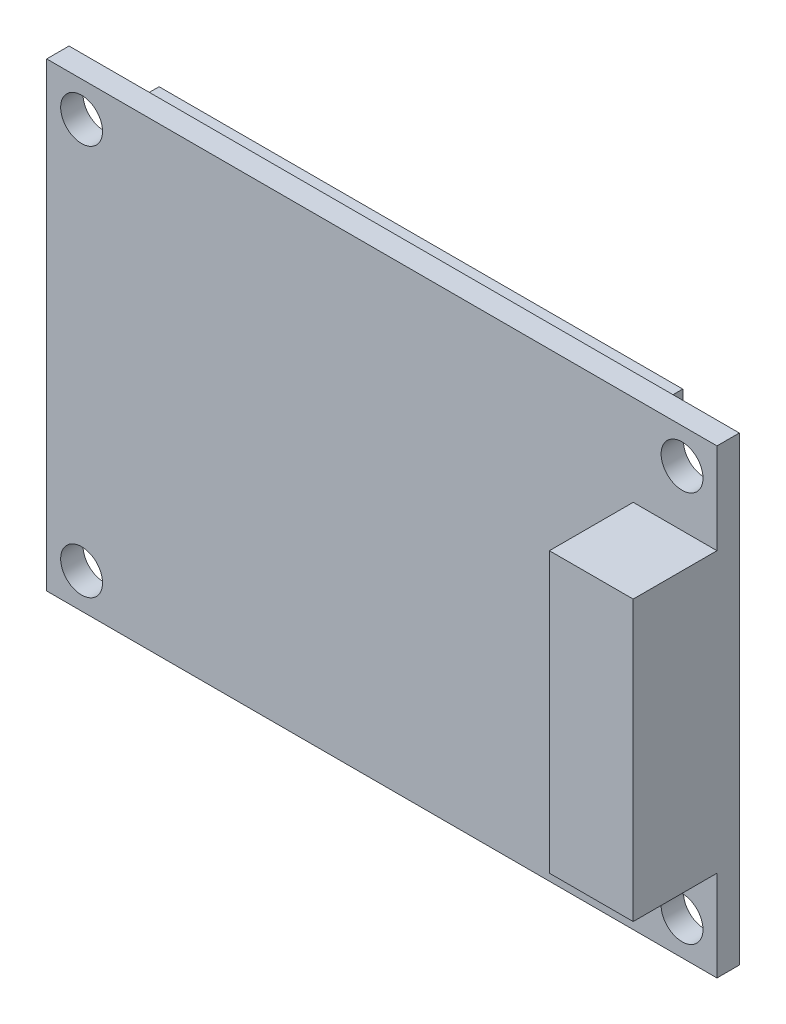
SolidWorks part; units mm, degrees
ref_plane "Plan de face" through (0, 0, 0) normal (0, 0, 1) x (1, 0, 0)
ref_plane "Plan de dessus" through (0, 0, 0) normal (0, 1, 0) x (1, 0, 0)
ref_plane "Plan de droite" through (0, 0, 0) normal (1, 0, 0) x (0, 0, -1)
sketch "BASE PCB" plane through (0, 0, 0) normal (0, 0, 1) x (1, 0, 0)
  line L0 (0, -18.15) -> (0, 18.15) construction
  line L1 (24, 16.5) -> (-24, 16.5)
  line L2 (24, 16.5) -> (24, -16.5)
  line L3 (24, -16.5) -> (-24, -16.5)
  line L4 (-24, 16.5) -> (-24, -16.5)
  line L5 (24, 16.5) -> (-24, -16.5) construction
  line L6 (24, -16.5) -> (-24, 16.5) construction
  line L8 (24, 10) -> (18, 10) construction
  line L9 (24, 10) -> (24, -10) construction
  line L10 (24, -10) -> (18, -10) construction
  line L11 (18, 10) -> (18, -10) construction
  circle A0 centre (-21.5, 14) radius 1.5
  circle A1 centre (-21.5, -14) radius 1.5
  circle A2 centre (21.5, -14) radius 1.5
  circle A3 centre (21.5, 14) radius 1.5
  point P0 (0, 0)
  point P10 (24, 0)
  point P21 (24, 0)
  dimension "D3" = 3
  dimension "D4" = 2.5
  dimension "D1" = 48
  dimension "D2" = 33
  dimension "D5" = 2.5
  dimension "D6" = 2.5
  dimension "D7" = 6
  dimension "D8" = 20
extrude "Base_PCB" add sketch "BASE PCB" along normal blind 1.6
sketch "Esquisse4" plane through (0, 0, 0) normal (0, 0, 1) x (1, 0, 0)
  line L1 (18.75, 16) -> (-18.75, 16)
  line L2 (18.75, 16) -> (18.75, -16)
  line L3 (18.75, -16) -> (-18.75, -16)
  line L4 (-18.75, 16) -> (-18.75, -16)
  line L5 (18.75, 16) -> (-18.75, -16) construction
  line L6 (18.75, -16) -> (-18.75, 16) construction
  point P0 (0, 0)
  dimension "D1" = 32
  dimension "D2" = 37.5
extrude "E-Ink_display" add sketch "Esquisse4" against normal blind 1.2
sketch "Esquisse5" plane through (0, 0, -1.2) normal (0, 0, -1) x (-1, 0, 0)
  line L1 (-16.75, -13.8) -> (10.85, -13.8)
  line L2 (-16.75, -13.8) -> (-16.75, 13.8)
  line L3 (-16.75, 13.8) -> (10.85, 13.8)
  line L4 (10.85, -13.8) -> (10.85, 13.8)
  line L7 (-18.75, -16) -> (-18.75, 16) construction
  point P6 (10.85, 0)
  dimension "D1" = 27.6
  dimension "D2" = 2
extrude "Display_200*200" cut sketch "Esquisse5" against normal blind 0.5
sketch "Esquisse6" plane through (0, 0, 1.6) normal (0, 0, 1) x (1, 0, 0)
  line L1 (18, 10) -> (24, 10)
  line L2 (18, 10) -> (18, -10)
  line L3 (18, -10) -> (24, -10)
  line L4 (24, 10) -> (24, -10)
extrude "Connecteur_8broches" add sketch "Esquisse6" along normal blind 6
